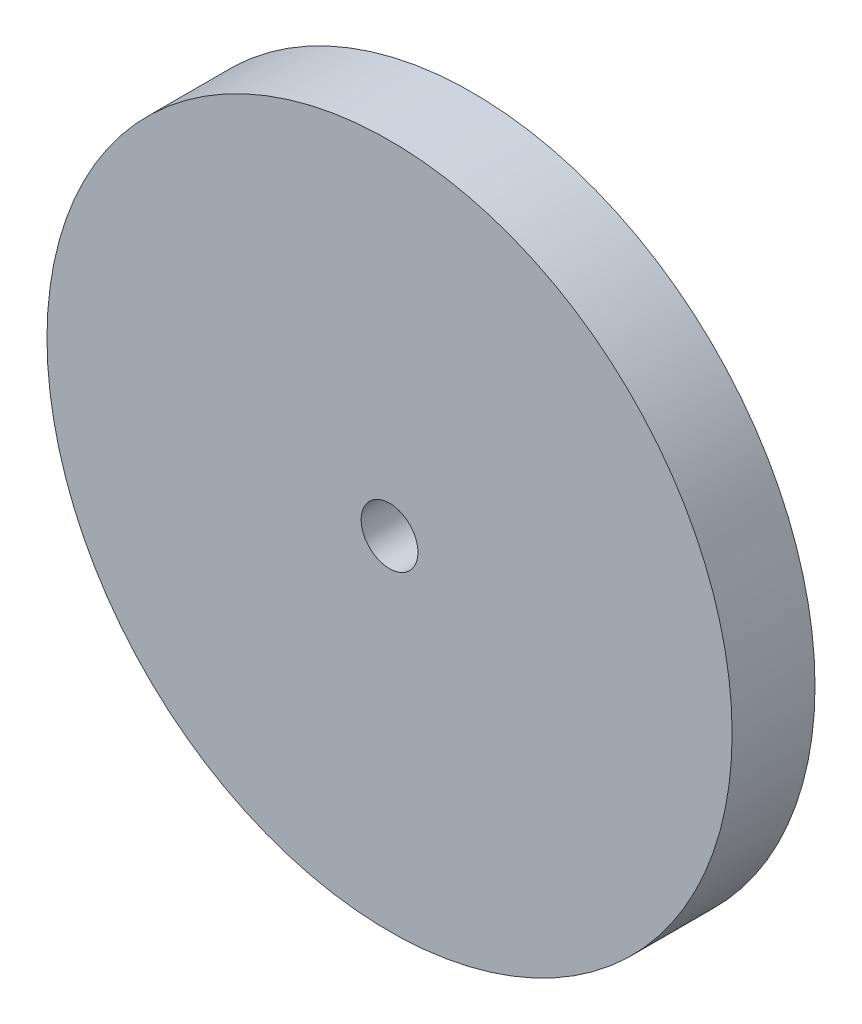
SolidWorks part; units mm, degrees
ref_plane "Front Plane" through (0, 0, 0) normal (0, 0, 1) x (1, 0, 0)
ref_plane "Top Plane" through (0, 0, 0) normal (0, 1, 0) x (1, 0, 0)
ref_plane "Right Plane" through (0, 0, 0) normal (1, 0, 0) x (0, 0, -1)
sketch "Sketch1" plane through (0, 0, 4.7625) normal (0, 0, 1) x (1, 0, 0)
  circle A1 centre (-35.5331, 0) radius 24.145
  circle A2 centre (-35.5331, 0) radius 2
  circle A3 centre (-35.5331, 0) radius 24.145 construction
  dimension "D1" = 4
extrude "Boss-Extrude1" add sketch "Sketch1" along normal blind 5.842
